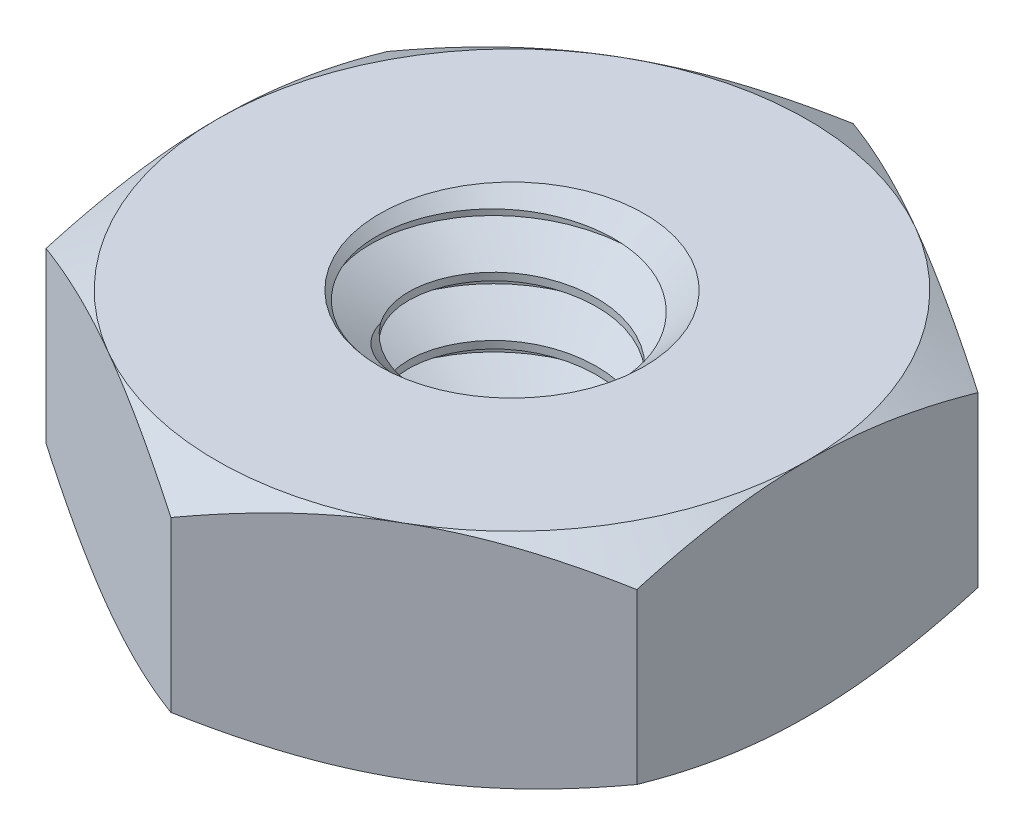
SolidWorks part; units mm, degrees
ref_plane "Front Plane" through (0, 0, 0) normal (0, 0, 1) x (1, 0, 0)
ref_plane "Top Plane" through (0, 0, 0) normal (0, 1, 0) x (1, 0, 0)
ref_plane "Right Plane" through (0, 0, 0) normal (1, 0, 0) x (0, 0, -1)
sketch "Sketch7" plane through (0, 0, 0) normal (0, 1, 0) x (1, 0, 0)
  line L0 (-3.175, 0) -> (3.175, 0) construction
  line L1 (-1.4224, 0) -> (1.4224, 0) construction
  line L2 (-3.175, 0) -> (-3.175, -0.635) construction
  point P4 (0, 0)
  point P8 (0, 0)
  dimension "Width" = 6.35
  dimension "Thread Size" = 2.8448
  dimension "Pitch" = 0.635
sketch "Sketch6" plane through (0, 0, 0) normal (1, 0, 0) x (0, 0, -1)
  line L0 (0, 1.1906) -> (0, -1.1906) construction
  point P4 (0, 0)
  dimension "Height" = 2.3813
sketch "Sketch1" plane through (0, 0, 0) normal (0, 1, 0) x (1, 0, 0)
  line L1 (-3.175, 1.8331) -> (-3.175, -1.8331)
  line L2 (-3.175, -1.8331) -> (0, -3.6662)
  line L3 (0, -3.6662) -> (3.175, -1.8331)
  line L4 (3.175, -1.8331) -> (3.175, 1.8331)
  line L5 (3.175, 1.8331) -> (0, 3.6662)
  line L6 (0, 3.6662) -> (-3.175, 1.8331)
  circle A0 centre (0, 0) radius 3.175 construction
  circle A1 centre (0, 0) radius 1.4224
extrude "Boss-Extrude1" add sketch "Sketch1" along normal mid plane 2.3813
sketch "Sketch5" plane through (0, 1.1906, 0) normal (0, 1, 0) x (1, 0, 0)
  circle A0 centre (0, 0) radius 3.175 construction
  circle A1 centre (0, 0) radius 3.175
extrude "Cut-Extrude2" cut sketch "Sketch5" against normal through all draft 60 flip side to cut
mirror "Mirror1" about plane through (0, 0, 0) normal (0, 1, 0) of "Cut-Extrude2"
sketch "Sketch14" plane through (0, 1.1906, 0) normal (0, 1, 0) x (1, 0, 0)
  line L0 (-1.4224, 0) -> (1.4224, 0) construction
  line L1 (0, 1.4224) -> (0, -1.4224) construction
  circle A0 centre (0, 0) radius 1.4224 construction
  point P7 (0, 0)
  point P11 (0, 0)
  point P12 (0, -1.4224)
  point P13 (-1.4224, 0)
  point P14 (0, 1.4224)
  point P15 (1.4224, 0)
sketch "Sketch8" plane through (0, 1.1906, 0) normal (0, 1, 0) x (1, 0, 0)
  circle A0 centre (0, 0) radius 1.4224 construction
  circle A1 centre (0, 0) radius 1.4224
extrude "Boss-Extrude2" add sketch "Sketch8" against normal up to surface (2.3813 mm away) separate body up to face at (0, -1.1906, 0)
sketch "Sketch9" plane through (0, 1.1906, 0) normal (0, 1, 0) x (1, 0, 0)
  circle A0 centre (0, 0) radius 1.4224 construction
  circle A1 centre (0, 0) radius 1.4224
extrude "Boss-Extrude3" add sketch "Sketch9" against normal up to surface (2.3813 mm away) up to face at (0, -1.1906, 0)
sketch "Sketch10" plane through (0, 1.1906, 0) normal (0, 1, 0) x (1, 0, 0)
  circle A0 centre (0, 0) radius 1.4224 construction
  circle A1 centre (0, 0) radius 1.4224
curve "Helix/Spiral1" pitch 0.635 height 3.0162 radius 1.4224 centre (0, 1.1906, 0) axis (0, -1, 0) start towards (0, 0, 1)
sketch "Sketch11" plane through (0, 0, 0) normal (1, 0, 0) x (0, 0, -1)
  line L0 (-1.4224, 1.1906) -> (-1.4224, 1.7463)
  line L1 (1.4224, 1.1906) -> (-1.4224, 1.1906) construction
  line L2 (-1.4224, 1.7463) -> (-1.01, 1.5081)
  line L3 (-1.01, 1.5081) -> (-1.01, 1.4288)
  line L4 (-1.01, 1.4288) -> (-1.4224, 1.1906)
  line L5 (-1.4224, 1.4684) -> (-1.01, 1.4684) construction
  line L6 (-1.2162, 1.6272) -> (-1.2162, 1.3097) construction
  spline S0 degree 3 poles (-1.4224, 1.1906) (-1.4224, 1.1773) (-1.3463, 1.1504) (-1.0218, 1.1102) (-0.5376, 1.07) (0.0306, 1.0298) (0.594, 0.9895) (1.0646, 0.9493) (1.3688, 0.9091) (1.4592, 0.8689) (1.3214, 0.8287) (0.9772, 0.7885) (0.4803, 0.7482) (-0.0917, 0.708) (-0.6494, 0.6678) (-1.1055, 0.6276) (-1.389, 0.5874) (-1.4553, 0.5472) (-1.2942, 0.5069) (-0.9309, 0.4667) (-0.4221, 0.4265) (0.1527, 0.3863) (0.7036, 0.3461) (1.1445, 0.3059) (1.4066, 0.2656) (1.4489, 0.2254) (1.2648, 0.1852) (0.883, 0.145) (0.3632, 0.1048) (-0.2133, 0.0646) (-0.7565, 0.0243) (-1.1815, -0.0159) (-1.4219, -0.0561) (-1.44, -0.0963) (-1.2331, -0.1365) (-0.8335, -0.1767) (-0.3036, -0.217) (0.2737, -0.2572) (0.8082, -0.2974) (1.2164, -0.3376) (1.4346, -0.3778) (1.4285, -0.418) (1.1992, -0.4583) (0.7825, -0.4985) (0.2436, -0.5387) (-0.3335, -0.5789) (-0.8584, -0.6191) (-1.2492, -0.6593) (-1.4448, -0.6996) (-1.4146, -0.7398) (-1.1633, -0.78) (-0.7302, -0.8202) (-0.183, -0.8604) (0.3927, -0.9006) (0.9071, -0.9409) (1.2798, -0.9811) (1.4524, -1.0213) (1.3981, -1.0615) (1.1253, -1.1017) (0.6766, -1.1419) (0.1222, -1.1822) (-0.4513, -1.2224) (-0.9543, -1.2626) (-1.3081, -1.3028) (-1.4576, -1.343) (-1.3792, -1.3832) (-1.0853, -1.4235) (-0.6218, -1.4637) (-0.0612, -1.5039) (0.5091, -1.5441) (0.9997, -1.5843) (1.3342, -1.6245) (1.4601, -1.6648) (1.3579, -1.705) (1.0433, -1.7452) (0.5665, -1.7854) (0.1874, -1.8123) (0, -1.8256) knots 0 0 0 0 0.013333 0.026667 0.04 0.053333 0.066667 0.08 0.093333 0.106667 0.12 0.133333 0.146667 0.16 0.173333 0.186667 0.2 0.213333 0.226667 0.24 0.253333 0.266667 0.28 0.293333 0.306667 0.32 0.333333 0.346667 0.36 0.373333 0.386667 0.4 0.413333 0.426667 0.44 0.453333 0.466667 0.48 0.493333 0.506667 0.52 0.533333 0.546667 0.56 0.573333 0.586667 0.6 0.613333 0.626667 0.64 0.653333 0.666667 0.68 0.693333 0.706667 0.72 0.733333 0.746667 0.76 0.773333 0.786667 0.8 0.813333 0.826667 0.84 0.853333 0.866667 0.88 0.893333 0.906667 0.92 0.933333 0.946667 0.96 0.973333 0.986667 1 1 1 1 construction
  dimension "D1" = 60
  dimension "D2" = 0.0794
  dimension "D3" = 0.3175
sweep "Cut-Sweep1" cut profiles "Sketch11" path "Helix/Spiral1" align with end faces yes
combine bodies "Combine1" operation type subtract main body 107 bodies to subtract 108
sketch "Sketch12" plane through (0, 1.1906, 0) normal (0, 1, 0) x (1, 0, 0)
  circle A1 centre (0, 0) radius 1.4224
  circle A2 centre (0, 0) radius 1.4224
  dimension "D1" = 0
extrude "Cut-Extrude3" cut sketch "Sketch12" against normal through all draft 45
sketch "Sketch13" plane through (0, -1.1906, 0) normal (0, -1, 0) x (1, 0, 0)
  circle A1 centre (0, 0) radius 1.4224
  circle A2 centre (0, 0) radius 1.4224
  dimension "D1" = 0
extrude "Cut-Extrude4" cut sketch "Sketch13" against normal through all draft 45
equation "\"D3@Helix/Spiral1\"=\"Height@Sketch6\"+\"Pitch@Sketch7\""
equation "\"Height@Boss-Extrude1\"=\"Height@Sketch6\""
equation "\"D4@Helix/Spiral1\"=\"Pitch@Sketch7\""
equation "\"D2@Sketch11\"=\"Pitch@Sketch7\"*.125"
equation "\"D3@Sketch11\"=\"Pitch@Sketch7\"*.5"
